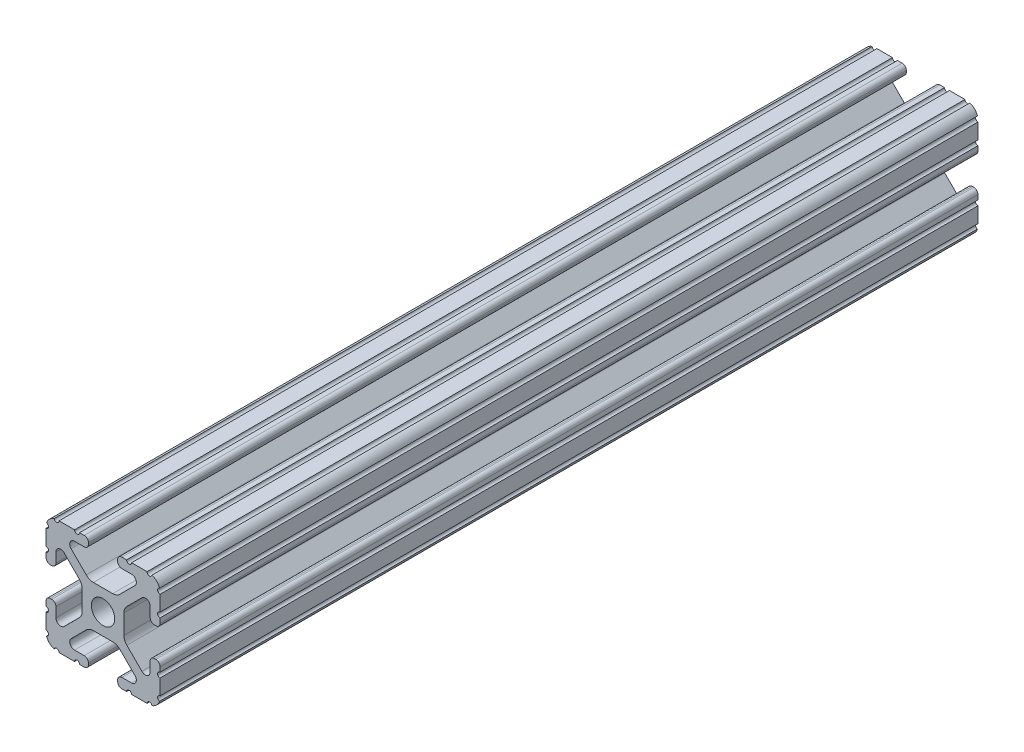
SolidWorks part; units mm, degrees
ref_plane "Front Plane" through (0, 0, 0) normal (0, 0, 1) x (1, 0, 0)
ref_plane "Top Plane" through (0, 0, 0) normal (0, 1, 0) x (1, 0, 0)
ref_plane "Right Plane" through (0, 0, 0) normal (1, 0, 0) x (0, 0, -1)
sketch "Sketch2" plane through (0, 0, 0) normal (0, 0, 1) x (1, 0, 0)
  line L0 (0, 12.7) -> (0, -12.7) construction
  line L1 (-12.7, 0) -> (12.7, 0) construction
  line L2 (3.2512, -12.7) -> (12.7, -12.7)
  line L3 (12.7, -12.7) -> (12.7, -3.2512)
  line L4 (3.2512, -12.7) -> (3.2512, -10.4902)
  line L5 (3.2512, -10.4902) -> (8.9276, -10.4902)
  line L6 (8.9276, -10.4902) -> (3.0856, -4.6482)
  line L7 (0, 0) -> (12.7, -12.7) construction
  line L8 (12.7, -3.2512) -> (10.4902, -3.2512)
  line L9 (10.4902, -3.2512) -> (10.4902, -8.9276)
  line L10 (10.4902, -8.9276) -> (4.6482, -3.0856)
  circle A0 centre (0, 0) radius 2.6035
  arc A1 (6.3485, -10.4902) -> (7.1039, -8.6665) centre (6.3485, -9.4219) ccw construction
  point P8 (0, -4.6482)
  dimension "Center Hole Diameter" = 5.207
  dimension "Rail Height" = 25.4
  dimension "Rail Width" = 25.4
  dimension "T-Slot Width" = 6.5024
  dimension "Slot Inner Width" = 14.8336
  dimension "Thickness" = 2.2098
  dimension "Slot Depth" = 5.842
  dimension "D1" = 2.2098
sketch "Sketch3" plane through (0, 0, 0) normal (1, 0, 0) x (0, 0, -1)
  line L0 (-91.0617, -12.7) -> (91.0617, -12.7) construction
  line L1 (-65.6617, 0) -> (65.6617, 0) construction
  line L2 (91.0617, 0) -> (-91.0617, 0) construction
sketch "Sketch4" plane through (0, 0, 0) normal (0, 0, 1) x (1, 0, 0)
  line L0 (4.1904, -12.7) -> (10.1173, -12.7)
  line L1 (3.2512, -12.7) -> (12.7, -12.7) construction
  line L2 (3.2512, -12.7) -> (3.2512, -10.4902) construction
  line L3 (3.2512, -10.4902) -> (8.9276, -10.4902) construction
  line L4 (3.2512, -11.4294) -> (3.2512, -11.7608)
  line L5 (4.1904, -10.4902) -> (6.3485, -10.4902)
  line L6 (0, -4.6482) -> (2.164, -4.6482)
  line L7 (8.9276, -10.4902) -> (3.0856, -4.6482) construction
  line L8 (3.7373, -5.2999) -> (7.1039, -8.6665)
  line L9 (12.7, -12.7) -> (12.7, -3.2512) construction
  line L10 (10.4902, -8.9276) -> (4.6482, -3.0856) construction
  line L11 (10.4902, -3.2512) -> (10.4902, -8.9276) construction
  line L12 (10.4902, -6.3485) -> (10.4902, -4.1904)
  line L13 (12.7, -3.2512) -> (10.4902, -3.2512) construction
  line L14 (11.4294, -3.2512) -> (11.7608, -3.2512)
  line L15 (12.7, -4.1904) -> (12.7, -10.1173)
  line L16 (8.6665, -7.1039) -> (5.2999, -3.7373)
  line L17 (4.6482, 0) -> (4.6482, -2.164)
  line L18 (-12.7, 0) -> (12.7, 0) construction
  line L19 (0, -4.6482) -> (0, -2.6035)
  line L20 (0, 12.7) -> (0, -12.7) construction
  line L21 (4.6482, 0) -> (2.6035, 0)
  arc A0 (3.2512, -11.7608) -> (4.1904, -12.7) centre (4.1904, -11.7608) ccw
  arc A2 (3.2512, -11.4294) -> (4.1904, -10.4902) centre (4.1904, -11.4294) cw
  arc A3 (6.3485, -10.4902) -> (7.1039, -8.6665) centre (6.3485, -9.4219) ccw
  arc A4 (2.164, -4.6482) -> (3.7373, -5.2999) centre (2.164, -6.8732) cw
  arc A5 (10.1173, -12.7) -> (12.7, -10.1173) centre (10.1173, -10.1173) ccw
  arc A6 (8.6665, -7.1039) -> (10.4902, -6.3485) centre (9.4219, -6.3485) ccw
  arc A7 (10.4902, -4.1904) -> (11.4294, -3.2512) centre (11.4294, -4.1904) cw
  arc A8 (11.7608, -3.2512) -> (12.7, -4.1904) centre (11.7608, -4.1904) cw
  arc A9 (5.2999, -3.7373) -> (4.6482, -2.164) centre (6.8732, -2.164) cw
  circle A10 centre (0, 0) radius 2.6035 construction
  arc A11 (0, -2.6035) -> (2.6035, 0) centre (0, 0) ccw
  dimension "D1" = 2.5827
  dimension "D2" = 2.225
  dimension "D3" = 0.9392
extrude "Boss-Extrude1" add sketch "Sketch4" along normal up to vertex (91.0617 mm away) from vertex up to point (0, -12.7, 91.0617) starting at point (0, -12.7, -91.0617)
sketch "Sketch5" plane through (0, 0, 0) normal (0, 0, 1) x (1, 0, 0)
  line L0 (3.2512, -12.7) -> (12.7, -12.7) construction
  line L1 (4.1904, -10.4902) -> (6.3485, -10.4902) construction
  line L3 (0, 0) -> (12.7, -12.7) construction
  line L4 (6.3485, -10.4902) -> (6.3485, -12.7) construction
  line L5 (8.9276, -10.4902) -> (3.0856, -4.6482) construction
  circle A0 centre (10.3562, -12.7) radius 0.5524
  circle A1 centre (5.796, -12.7) radius 0.5524
  circle A2 centre (12.7, -10.3562) radius 0.5524
  circle A3 centre (12.7, -5.796) radius 0.5524
  point P10 (5.2694, -10.4902)
  point P12 (9.4219, -6.3485)
  dimension "D1" = 1.1049
extrude "Cut-Extrude1" cut sketch "Sketch5" against normal through all both and the other way through all
mirror "Mirror1" about plane through (0, 0, 0) normal (1, 0, 0) of bodies 137 134
mirror "Mirror2" about plane through (0, 0, 0) normal (0, 1, 0) of bodies 135
equation "\"D1@Sketch2\"=\"Thickness@Sketch2\""
equation "\"D2@Sketch4\"=\"Slot Inner Width@Sketch2\"*0.15"
equation "\"D1@Sketch4\"=\"D3@Sketch4\"*2.75"
equation "\"D3@Sketch4\"=\"Thickness@Sketch2\"*0.425"
equation "\"D1@Sketch5\"=\"Thickness@Sketch2\"*0.5"
equation "\"D1@Boss-Extrude1\"=\"Length@Sketch3\""
